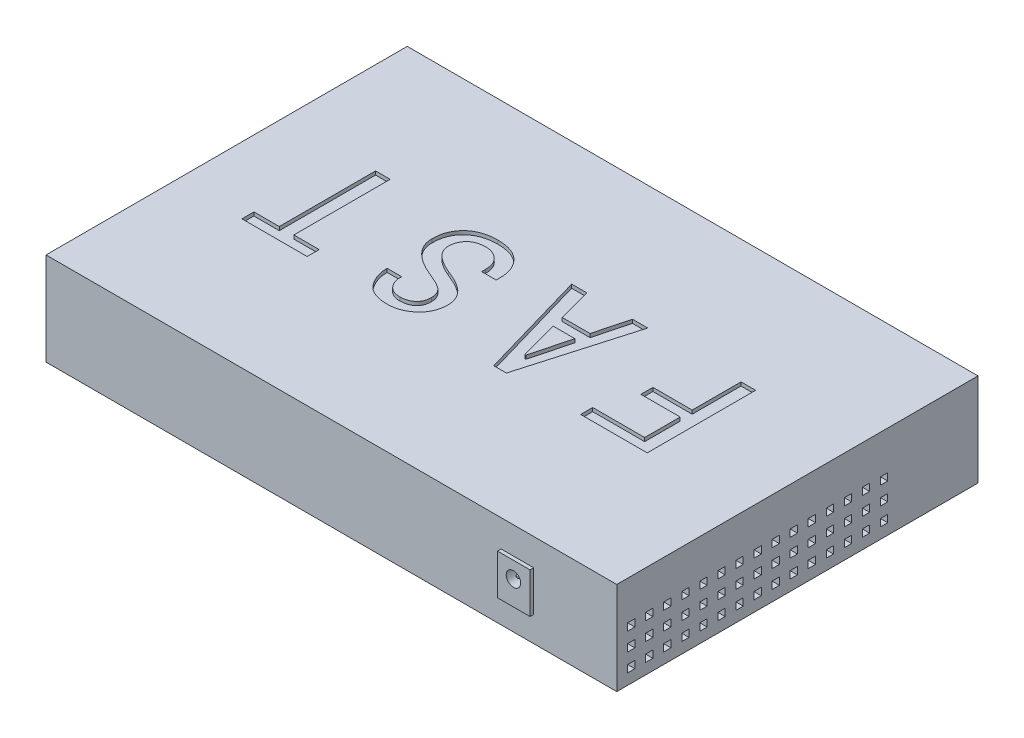
SolidWorks part; units mm, degrees
ref_plane "前视基准面" through (0, 0, 0) normal (0, 0, 1) x (1, 0, 0)
ref_plane "上视基准面" through (0, 0, 0) normal (0, 1, 0) x (1, 0, 0)
ref_plane "右视基准面" through (0, 0, 0) normal (1, 0, 0) x (0, 0, -1)
sketch "草图1" plane through (0, 0, 0) normal (0, 1, 0) x (1, 0, 0)
  line L1 (-79, -50) -> (79, -50)
  line L2 (-79, -50) -> (-79, 50)
  line L3 (-79, 50) -> (79, 50)
  line L4 (79, -50) -> (79, 50)
  line L5 (-79, -50) -> (79, 50) construction
  line L6 (-79, 50) -> (79, -50) construction
  point P0 (0, 0)
  dimension "D1" = 158
  dimension "D2" = 100
extrude "凸台-拉伸1" add sketch "草图1" along normal blind 25.7
sketch "草图2" plane through (0, 0, -50) normal (0, 0, -1) x (-1, 0, 0)
  line L0 (-50.7, 9.4) -> (-50.7, 32.9915) construction
  line L5 (-44.7, 9.4) -> (-56.7, 9.4)
  line L6 (-56.7, 9.4) -> (-56.7, 16.4)
  line L7 (-56.7, 16.4) -> (-53.8, 16.4)
  line L8 (-53.8, 16.4) -> (-53.8, 17.9)
  line L9 (-53.8, 17.9) -> (-52.75, 17.9)
  line L10 (-52.75, 17.9) -> (-52.75, 19.4)
  line L11 (-52.75, 19.4) -> (-48.65, 19.4)
  line L12 (-48.65, 17.9) -> (-48.65, 19.4)
  line L13 (-47.6, 17.9) -> (-48.65, 17.9)
  line L14 (-47.6, 16.4) -> (-47.6, 17.9)
  line L15 (-44.7, 16.4) -> (-47.6, 16.4)
  line L16 (-44.7, 9.4) -> (-44.7, 16.4)
  line L17 (-79, 0) -> (79, 0) construction
  line L18 (-79, 25.7) -> (-79, 0) construction
  point P10 (-50.7, 19.4)
  dimension "D1" = 12
  dimension "D2" = 6.2
  dimension "D3" = 4.1
  dimension "D4" = 10
  dimension "D5" = 7
  dimension "D6" = 8.5
  dimension "D7" = 9.4
  dimension "D8" = 22.3
extrude "切除-拉伸1" cut sketch "草图2" against normal blind 11
pattern_linear "阵列(线性)1" count 8 spacing 14.7 along (-1, 0, 0) of "切除-拉伸1"
sketch "草图3" plane through (0, 0, -50) normal (0, 0, -1) x (-1, 0, 0)
  line L0 (-79, 25.7) -> (-79, 0) construction
  line L1 (-59, 20.7) -> (59, 20.7)
  line L2 (-59, 20.7) -> (-59, 7.2)
  line L3 (-59, 7.2) -> (59, 7.2)
  line L4 (59, 20.7) -> (59, 7.2)
  line L5 (-79, 25.7) -> (79, 25.7) construction
  line L6 (-60, 21.7) -> (60, 21.7)
  line L7 (60, 21.7) -> (60, 6.2)
  line L8 (-60, 6.2) -> (60, 6.2)
  line L9 (-60, 21.7) -> (-60, 6.2)
  dimension "D1" = 118
  dimension "D2" = 13.5
  dimension "D3" = 20
  dimension "D4" = 5
  dimension "D5" = 1
extrude "切除-拉伸2" cut sketch "草图3" against normal blind 13
sketch "草图4" plane through (0, 25.7, 0) normal (0, 1, 0) x (1, 0, 0)
  text T0 "<r180>TSAF" font "黑体" height 30
  point P1 (-51.0911, -11.3827)
  point P2 (-55.5097, -13.3365)
  point P3 (58.666, 26.5977)
  point P4 (-28.4475, 23.3969)
  point P5 (-51.6233, 23.5124)
  point P6 (-41.2038, 24.6208)
  point P7 (-40.5387, 16.6399)
extrude "切除-拉伸3" cut sketch "草图4" against normal blind 1
sketch "草图5" plane through (0, 0, 50) normal (0, 0, 1) x (1, 0, 0)
  line L0 (-79, 25.7) -> (79, 25.7) construction
  line L1 (79, 25.7) -> (79, 0) construction
  circle A0 centre (51.4, 13.7) radius 2
  circle A1 centre (51.4, 13.7) radius 0.5
  dimension "D1" = 1
  dimension "D2" = 4
  dimension "D3" = 12
  dimension "D4" = 27.6
extrude "切除-拉伸4" cut sketch "草图5" against normal blind 8
fillet "圆角1" radius 0.4 1 edges at (51.9, 13.7, 50)
sketch "草图6" plane through (0, 0, 50) normal (0, 0, 1) x (1, 0, 0)
  line L0 (51.4, 13.8) -> (51.4, 29.7475) construction
  line L1 (-79, 0) -> (79, 0) construction
  line L2 (47, 7) -> (56, 7)
  line L3 (47, 7) -> (47, 18.2)
  line L4 (47, 18.2) -> (56, 18.2)
  line L5 (56, 7) -> (56, 18.2)
  line L6 (47, 7) -> (56, 18.2) construction
  line L7 (47, 18.2) -> (56, 7) construction
  line L8 (79, 25.7) -> (79, 0) construction
  circle A0 centre (51.4, 13.7) radius 0.1 construction
  circle A1 centre (51.4, 13.7) radius 2 construction
  circle A2 centre (51.4, 13.7) radius 2
  point P5 (51.5, 12.6)
  dimension "D1" = 11.2
  dimension "D2" = 9
  dimension "D3" = 7
  dimension "D4" = 23
extrude "凸台-拉伸2" add sketch "草图6" along normal blind 1
sketch "草图7" plane through (79, 0, 0) normal (1, 0, 0) x (0, 0, -1)
  line L0 (-50, 7) -> (-50, 18.2) construction
  line L1 (-47, 15) -> (-45, 15)
  line L2 (-47, 15) -> (-47, 13)
  line L3 (-47, 13) -> (-45, 13)
  line L4 (-45, 15) -> (-45, 13)
  line L5 (-50, 0) -> (50, 0) construction
  dimension "D1" = 2
  dimension "D2" = 2
  dimension "D3" = 3
  dimension "D4" = 13
extrude "切除-拉伸5" cut sketch "草图7" against normal blind 10
pattern_linear "阵列(线性)2" count 15 spacing 5 along (0, 0, -1) count 3 spacing 5 along (0, -1, 0) of "切除-拉伸5"
mirror "镜向1" about plane through (0, 0, 0) normal (1, 0, 0) of "阵列(线性)2"
sketch "草图8" plane through (0, 0, -50) normal (0, 0, -1) x (-1, 0, 0)
  line L0 (79, 25.7) -> (79, 0) construction
  line L1 (62, 12) -> (68, 12)
  line L2 (62, 12) -> (62, 8)
  line L3 (62, 8) -> (68, 8)
  line L4 (68, 12) -> (68, 8)
  line L5 (-79, 0) -> (79, 0) construction
  dimension "D1" = 4
  dimension "D2" = 6
  dimension "D3" = 11
  dimension "D4" = 8
extrude "切除-拉伸6" cut sketch "草图8" against normal blind 5
sketch "草图9" plane through (0, 0, -45) normal (0, 0, -1) x (-1, 0, 0)
  line L0 (68, 10) -> (62, 10) construction
  line L1 (65.7, 11.5) -> (67.7, 11.5)
  line L2 (65.7, 11.5) -> (65.7, 8.5)
  line L3 (65.7, 8.5) -> (67.7, 8.5)
  line L4 (67.7, 11.5) -> (67.7, 8.5)
  line L5 (68, 8) -> (68, 12) construction
  line L6 (62, 12) -> (62, 8) construction
  point P10 (67.7, 10)
  dimension "D1" = 2
  dimension "D2" = 3
  dimension "D3" = 0.3
extrude "凸台-拉伸3" add sketch "草图9" along normal blind 5
sketch "草图10" plane through (0, 0, -50) normal (0, 0, -1) x (-1, 0, 0)
  line L0 (-79, 25.7) -> (-79, 0) construction
  line L1 (-79, 0) -> (79, 0) construction
  circle A0 centre (-70.3, 9) radius 1.1
  circle A1 centre (-70.3, 9) radius 1
  dimension "D1" = 2
  dimension "D2" = 2.2
  dimension "D3" = 8.7
  dimension "D4" = 9
extrude "切除-拉伸7" cut sketch "草图10" against normal blind 1
fillet "圆角2" radius 1 1 edges at (69.3, 9, -50)
pattern_linear "阵列(线性)4" count 2 spacing 5 along (-1, 0, 0) of "圆角2", "切除-拉伸7"
